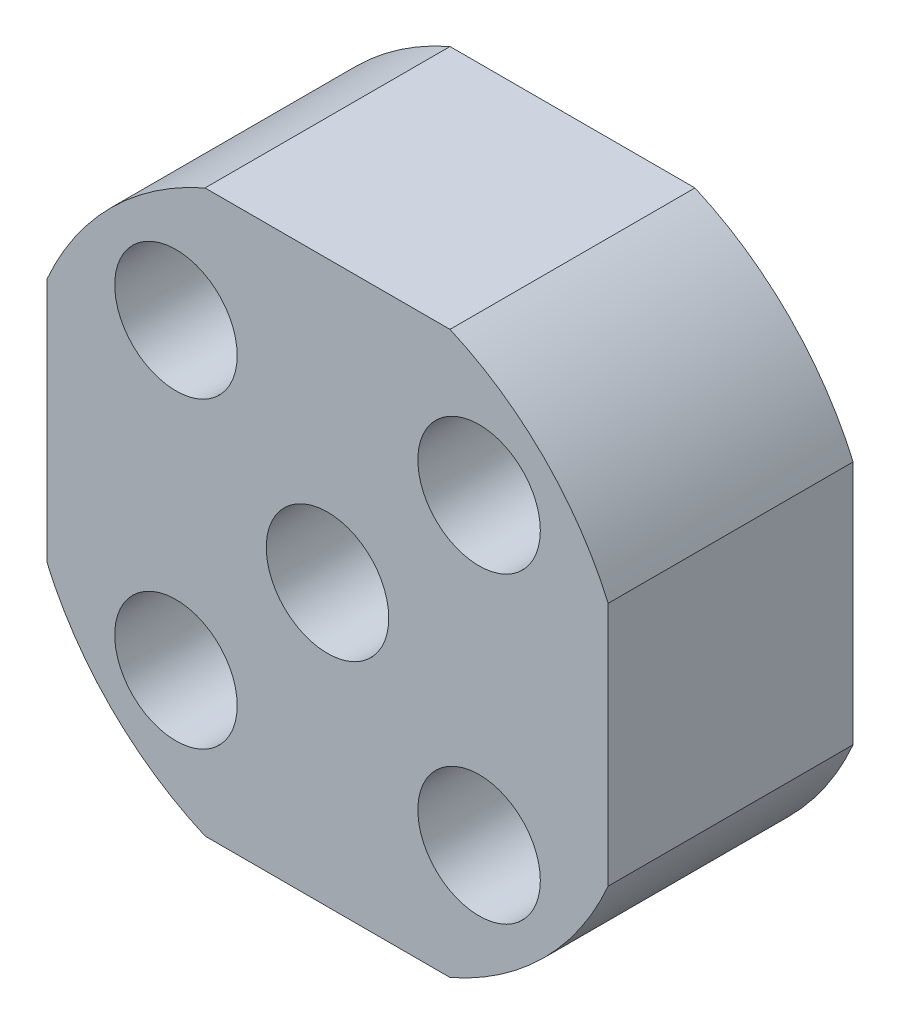
SolidWorks part; units mm, degrees
ref_plane "Front Plane" through (0, 0, 0) normal (0, 0, 1) x (1, 0, 0)
ref_plane "Top Plane" through (0, 0, 0) normal (0, 1, 0) x (1, 0, 0)
ref_plane "Right Plane" through (0, 0, 0) normal (1, 0, 0) x (0, 0, -1)
sketch "Sketch2" plane through (0, 0, 0) normal (0, 0, 1) x (1, 0, 0)
  line L1 (1, 2.2913) -> (-1, 2.2913)
  line L2 (2.2913, 1) -> (2.2913, -1)
  line L3 (-2.2913, 1) -> (-2.2913, -1)
  line L4 (-1, -2.2913) -> (1, -2.2913)
  line L5 (-2.2913, 0) -> (2.2913, 0) construction
  line L6 (0, 2.2913) -> (0, -2.2913) construction
  line L7 (0, 0) -> (1.7678, 1.7678) construction
  arc A6 (-2.2913, -1) -> (-1, -2.2913) centre (0, 0) ccw
  arc A7 (-1, 2.2913) -> (-2.2913, 1) centre (0, 0) ccw
  arc A8 (2.2913, 1) -> (1, 2.2913) centre (0, 0) ccw
  arc A9 (1, -2.2913) -> (2.2913, -1) centre (0, 0) ccw
  circle A10 centre (0, 0) radius 0.5
  circle A11 centre (1.2374, 1.2374) radius 0.5
  circle A12 centre (1.2374, -1.2374) radius 0.5
  circle A13 centre (-1.2374, -1.2374) radius 0.5
  circle A14 centre (-1.2374, 1.2374) radius 0.5
  point P26 (0, 0)
  dimension "D1" = 5
  dimension "D3" = 1
  dimension "D4" = 1
  dimension "D2" = 2
  dimension "D5" = 1.75
  dimension "D6" = 4
extrude "Boss-Extrude1" add sketch "Sketch2" along normal blind 2
sketch "Sketch3" plane through (0, 0, 0) normal (0, 1, 0) x (1, 0, 0)
  line L0 (-2.2913, -1) -> (2.2913, -1)
  line L1 (-2.2913, -2) -> (-2.2913, 0) construction
  line L2 (2.2913, -2) -> (2.2913, 0) construction
  line L3 (0, -1) -> (0, 1.3336)
sketch "Sketch4" plane through (0, 0, 0) normal (0, 1, 0) x (1, 0, 0)
  line L0 (1, -2) -> (-1, -2) construction
  line L1 (0, -1) -> (0, -3.09) construction
  line L2 (-2.2913, -1) -> (2.2913, -1) construction
  line L3 (1, 0) -> (-1, 0) construction
  line L4 (0, 1.09) -> (0, -1) construction
  circle A0 centre (0, -3.09) radius 1.2
  circle A1 centre (0, 1.09) radius 1.2
  dimension "D2" = 2.4
  dimension "D3" = 2.4
  dimension "D1" = 1.09
  dimension "D4" = 1.09
ref_plane "Plane1" through (0, 0, 0) normal (0, 1, 0) x (1, 0, 0)
ref_axis "Axis1" through (0, 0, 2) along (0, 0, -1)
ref_point "Point2"
